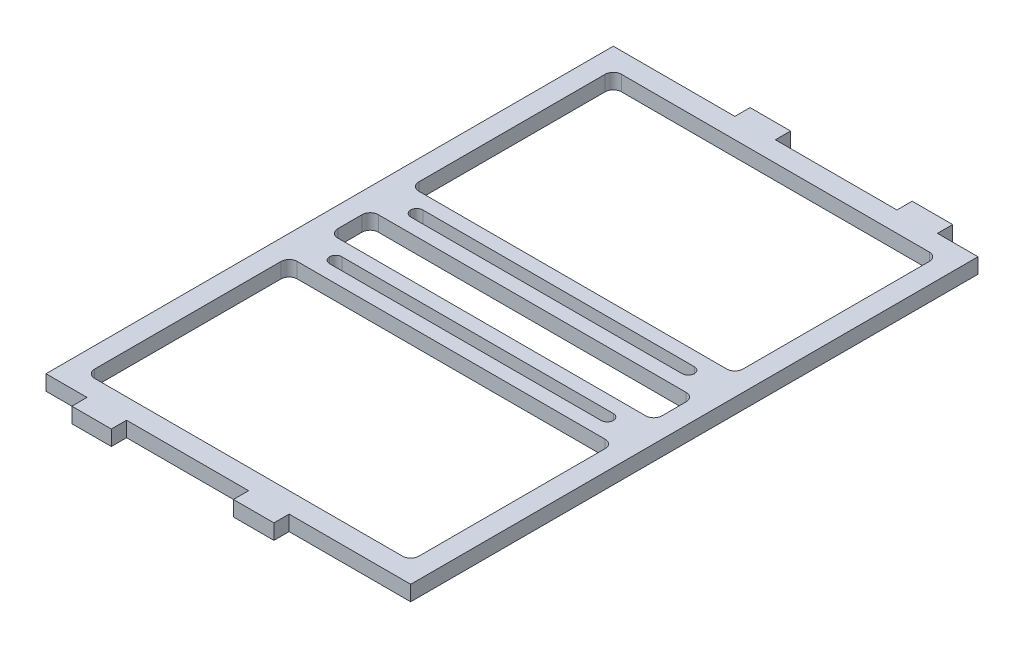
SolidWorks part; units mm, degrees
material "6061-T6 (SS)"
ref_plane "Front Plane" through (0, 0, 0) normal (0, 0, 1) x (1, 0, 0)
ref_plane "Top Plane" through (0, 0, 0) normal (0, 1, 0) x (1, 0, 0)
ref_plane "Right Plane" through (0, 0, 0) normal (1, 0, 0) x (0, 0, -1)
sketch "Sketch1" plane through (0, 0, 0) normal (0, 1, 0) x (1, 0, 0)
  line L0 (50.8, 82.55) -> (-50.8, 82.55)
  line L1 (57.15, 88.9) -> (-57.15, 88.9)
  line L2 (57.15, 88.9) -> (57.15, -88.9)
  line L3 (57.15, -88.9) -> (-57.15, -88.9)
  line L4 (-57.15, 88.9) -> (-57.15, -88.9)
  line L5 (57.15, 88.9) -> (-57.15, -88.9) construction
  line L6 (57.15, -88.9) -> (-57.15, 88.9) construction
  line L7 (-50.8, 82.55) -> (-50.8, -82.55)
  line L8 (50.8, -82.55) -> (-50.8, -82.55)
  line L9 (50.8, 82.55) -> (50.8, -82.55)
  point P0 (0, 0)
  dimension "D1" = 114.3
  dimension "D2" = 177.8
  dimension "D3" = 6.35
extrude "Boss-Extrude1" add sketch "Sketch1" along normal blind 4.7625
sketch "Sketch2" plane through (0, 0, 88.9) normal (0, 0, 1) x (1, 0, 0)
  line L0 (-57.15, 2.3813) -> (57.15, 2.3813) construction
  line L1 (-57.15, 4.7625) -> (-57.15, 0) construction
  line L2 (57.15, 4.7625) -> (57.15, 0) construction
  line L3 (-57.15, 0) -> (57.15, 0) construction
  line L4 (-31.9066, 4.7625) -> (-44.2934, 4.7625)
  line L5 (-31.9066, 4.7625) -> (-31.9066, 0)
  line L6 (-31.9066, 0) -> (-44.2934, 0)
  line L7 (-44.2934, 4.7625) -> (-44.2934, 0)
  line L8 (-31.9066, 4.7625) -> (-44.2934, 0) construction
  line L9 (-31.9066, 0) -> (-44.2934, 4.7625) construction
  line L11 (19.05, 4.7625) -> (6.35, 4.7625)
  line L12 (19.05, 4.7625) -> (19.05, 0)
  line L13 (19.05, 0) -> (6.35, 0)
  line L14 (6.35, 4.7625) -> (6.35, 0)
  line L15 (19.05, 4.7625) -> (6.35, 0) construction
  line L16 (19.05, 0) -> (6.35, 4.7625) construction
  point P6 (-38.1, 2.3813)
  point P13 (12.7, 2.3813)
  dimension "D1" = 19.05
  dimension "D2" = 50.8
  dimension "D3" = 12.7
extrude "Boss-Extrude2" add sketch "Sketch2" along normal blind 4.7625
sketch "Sketch3" plane through (0, 0, -88.9) normal (0, 0, -1) x (-1, 0, 0)
  line L0 (-57.15, 2.3813) -> (57.15, 2.3813) construction
  line L1 (-57.15, 4.7625) -> (-57.15, 0) construction
  line L2 (57.15, 4.7625) -> (57.15, 0) construction
  line L3 (-57.15, 0) -> (57.15, 0) construction
  line L4 (-31.75, 4.7625) -> (-44.45, 4.7625)
  line L5 (-31.75, 4.7625) -> (-31.75, 0)
  line L6 (-31.75, 0) -> (-44.45, 0)
  line L7 (-44.45, 4.7625) -> (-44.45, 0)
  line L8 (-31.75, 4.7625) -> (-44.45, 0) construction
  line L9 (-31.75, 0) -> (-44.45, 4.7625) construction
  line L11 (19.05, 4.7625) -> (6.35, 4.7625)
  line L12 (19.05, 4.7625) -> (19.05, 0)
  line L13 (19.05, 0) -> (6.35, 0)
  line L14 (6.35, 4.7625) -> (6.35, 0)
  line L15 (19.05, 4.7625) -> (6.35, 0) construction
  line L16 (19.05, 0) -> (6.35, 4.7625) construction
  point P6 (-38.1, 2.3812)
  point P13 (12.7, 2.3812)
  dimension "D1" = 12.7
  dimension "D2" = 12.7
  dimension "D3" = 19.05
  dimension "D4" = 50.8
extrude "Boss-Extrude3" add sketch "Sketch3" along normal blind 4.7625
sketch "Sketch4" plane through (0, 4.7625, 0) normal (0, 1, 0) x (-1, 0, 0)
  line L0 (0, -82.55) -> (0, 82.55) construction
  line L1 (-50.8, -82.55) -> (50.8, -82.55) construction
  line L2 (50.8, 82.55) -> (-50.8, 82.55) construction
  line L4 (6.35, -82.55) -> (-6.35, -82.55)
  line L5 (6.35, -82.55) -> (6.35, 82.55)
  line L6 (6.35, 82.55) -> (-6.35, 82.55)
  line L7 (-6.35, -82.55) -> (-6.35, 82.55)
  line L8 (6.35, -82.55) -> (-6.35, 82.55) construction
  line L9 (6.35, 82.55) -> (-6.35, -82.55) construction
  point P6 (0, 0)
  dimension "D1" = 12.7
extrude "Boss-Extrude4" [suppressed] add sketch "Sketch4" against normal blind 4.7625
hole_wizard "#6 Clearance Hole1" [suppressed] positions "Sketch6" profile "Sketch5" hole size "#6" standard "Ansi Inch"
sketch "Sketch6" plane through (0, 0, 0) normal (0, -1, 0) x (1, 0, 0)
  line L0 (0, -82.55) -> (0, 82.55) construction
  line L1 (31.75, -82.55) -> (-6.35, -82.55) construction
  line L2 (-31.9066, 82.55) -> (6.35, 82.55) construction
  point P0 (0, 60.5257)
  point P1 (0, 37.9247)
  point P3 (0, -60.325)
  dimension "D1" = 98.2497
  dimension "D2" = 22.6009
  dimension "D3" = 60.325
sketch "Sketch5" plane through (0, 0, 60.5257) normal (1, 0, 0) x (0, 0, -1)
  line L0 (0, 0) -> (0, 26.5408)
  line L1 (0, 26.5408) -> (1.8986, 25.4)
  line L2 (1.8986, 25.4) -> (1.8986, 0)
  line L5 (1.8986, 0) -> (0, 0)
  line L10 (0, 26.5408) -> (-1.8986, 25.4) construction
  line L11 (0, -6.35) -> (0, 107.95) construction
  dimension "Hole Dia." = 3.7973
  dimension "Hole Depth" = 25.4
  dimension "Drill Angle" = 118
sketch "Sketch7" plane through (0, 4.7625, 0) normal (0, 1, 0) x (1, 0, 0)
  line L0 (57.15, 0) -> (-57.15, 0) construction
  line L1 (57.15, -88.9) -> (57.15, 88.9) construction
  line L2 (-57.15, 88.9) -> (-57.15, -88.9) construction
  line L4 (57.15, 19.05) -> (-57.15, 19.05)
  line L5 (57.15, 19.05) -> (57.15, 6.35)
  line L6 (57.15, 6.35) -> (-57.15, 6.35)
  line L7 (-57.15, 19.05) -> (-57.15, 6.35)
  line L8 (57.15, 19.05) -> (-57.15, 6.35) construction
  line L9 (57.15, 6.35) -> (-57.15, 19.05) construction
  line L10 (57.15, -6.35) -> (-57.15, -6.35)
  line L11 (57.15, -6.35) -> (57.15, -19.05)
  line L12 (57.15, -19.05) -> (-57.15, -19.05)
  line L13 (-57.15, -6.35) -> (-57.15, -19.05)
  line L14 (57.15, -6.35) -> (-57.15, -19.05) construction
  line L15 (57.15, -19.05) -> (-57.15, -6.35) construction
  line L16 (44.45, 14.605) -> (-44.45, 14.605)
  line L17 (44.45, 14.605) -> (44.45, 10.795)
  line L18 (44.45, 10.795) -> (-44.45, 10.795)
  line L19 (-44.45, 14.605) -> (-44.45, 10.795)
  line L20 (44.45, 14.605) -> (-44.45, 10.795) construction
  line L21 (44.45, 10.795) -> (-44.45, 14.605) construction
  line L22 (44.45, -10.795) -> (-44.45, -10.795)
  line L23 (44.45, -10.795) -> (44.45, -14.605)
  line L24 (44.45, -14.605) -> (-44.45, -14.605)
  line L25 (-44.45, -10.795) -> (-44.45, -14.605)
  line L26 (44.45, -10.795) -> (-44.45, -14.605) construction
  line L27 (44.45, -14.605) -> (-44.45, -10.795) construction
  point P6 (0, 12.7)
  point P11 (0, -12.7)
  point P16 (0, 12.7)
  point P22 (0, -12.7)
  dimension "D1" = 12.7
  dimension "D2" = 12.7
  dimension "D3" = 12.7
  dimension "D4" = 12.7
  dimension "D5" = 88.9
  dimension "D6" = 88.9
  dimension "D7" = 3.81
  dimension "D8" = 3.81
extrude "Boss-Extrude5" add sketch "Sketch7" against normal blind 4.7625
fillet "Fillet1" radius 2.54 12 edges at (50.8, 2.3813, 6.35) (50.8, 2.3813, -6.35) (50.8, 2.3813, 19.05) (50.8, 2.3813, 82.55) (-50.8, 2.3813, 82.55) (-50.8, 2.3813, 19.05) (-50.8, 2.3813, 6.35) (-50.8, 2.3813, -6.35) (-50.8, 2.3813, -19.05) (50.8, 2.3813, -19.05) (-50.8, 2.3813, -82.55) (50.8, 2.3813, -82.55)
fillet "Fillet2" radius 1.905 8 edges at (-44.45, 2.3813, -10.795) (-44.45, 2.3813, -14.605) (44.45, 2.3813, -10.795) (44.45, 2.3813, -14.605) (44.45, 2.3813, 14.605) (44.45, 2.3813, 10.795) (-44.45, 2.3813, 14.605) (-44.45, 2.3813, 10.795)
